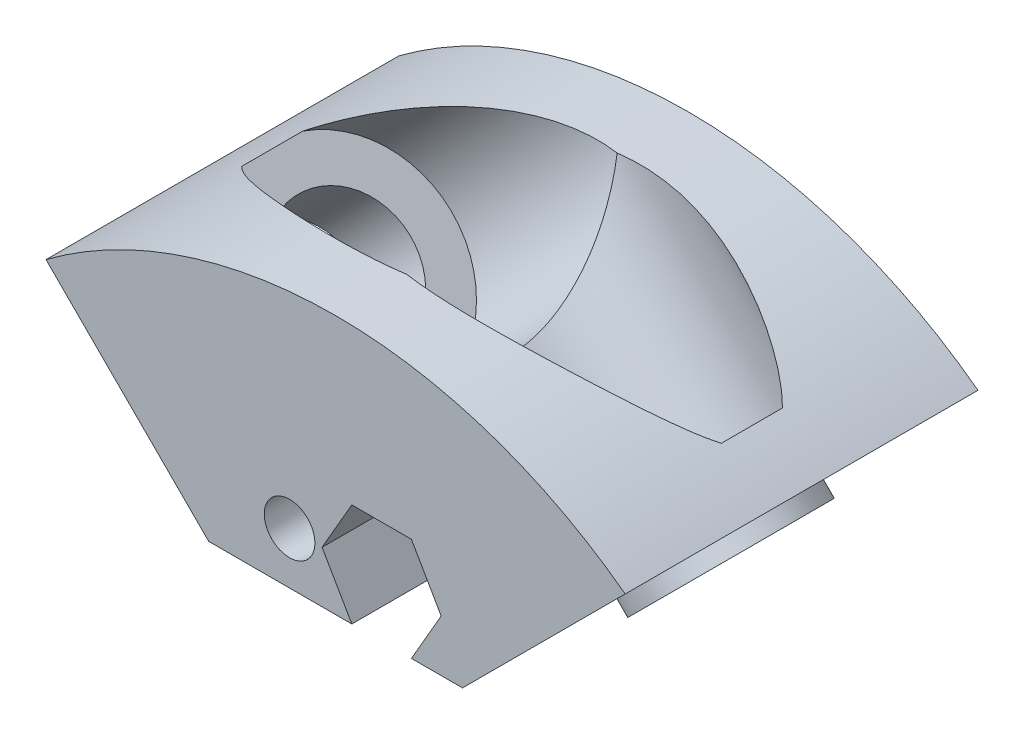
SolidWorks part; units mm, degrees
ref_plane "Front Plane" through (0, 0, 0) normal (0, 0, 1) x (1, 0, 0)
ref_plane "Top Plane" through (0, 0, 0) normal (0, 1, 0) x (1, 0, 0)
ref_plane "Right Plane" through (0, 0, 0) normal (1, 0, 0) x (0, 0, -1)
sketch "Sketch4" plane through (0, 0, 0) normal (0, 0, 1) x (1, 0, 0)
  line L0 (-6.5054, 11.4551) -> (-22.0617, 27.0115) construction
  line L1 (-6.5054, 11.4551) -> (-11.4551, 6.5054) construction
  line L2 (-22.0617, 27.0115) -> (-27.0115, 22.0617) construction
  line L3 (-11.4551, 6.5054) -> (-27.0115, 22.0617) construction
  line L4 (-6.5054, 11.4551) -> (-27.0115, 22.0617) construction
  line L5 (-22.0617, 27.0115) -> (-11.4551, 6.5054) construction
  line L6 (27.0115, 22.0617) -> (11.4551, 6.5054) construction
  line L7 (27.0115, 22.0617) -> (22.0617, 27.0115) construction
  line L8 (11.4551, 6.5054) -> (6.5054, 11.4551) construction
  line L9 (22.0617, 27.0115) -> (6.5054, 11.4551) construction
  line L10 (27.0115, 22.0617) -> (6.5054, 11.4551) construction
  line L11 (11.4551, 6.5054) -> (22.0617, 27.0115) construction
  line L12 (0, 0) -> (24.5366, 24.5366) construction
  line L13 (0, 0) -> (-8.9803, 8.9803) construction
  line L14 (0, -981.4314) -> (0, 49018.5686) construction
  line L15 (-18.8798, 25.2437) -> (-8.2731, 14.6371)
  line L16 (8.2731, 14.6371) -> (18.8798, 25.2437)
  line L17 (-16.7584, 16.7584) -> (-13.5765, 19.9404) construction
  line L18 (16.7584, 16.7584) -> (13.5765, 19.9404) construction
  line L19 (-18.1726, 23.1224) -> (-10.3945, 15.3442)
  line L20 (18.1726, 23.1224) -> (10.3945, 15.3442)
  line L21 (-10.3945, 15.3442) -> (-9.6874, 16.0513)
  line L22 (-9.6874, 16.0513) -> (-8.2731, 14.6371)
  line L23 (10.3945, 15.3442) -> (9.6874, 16.0513)
  line L24 (9.6874, 16.0513) -> (8.2731, 14.6371)
  line L25 (18.1726, 23.1224) -> (17.4655, 23.8295)
  line L26 (17.4655, 23.8295) -> (18.8798, 25.2437)
  line L27 (-18.8798, 25.2437) -> (-17.4655, 23.8295)
  line L28 (-17.4655, 23.8295) -> (-18.1726, 23.1224)
  line L29 (-14.2836, 19.2333) -> (-13.5765, 19.9404)
  line L30 (14.2836, 19.2333) -> (13.5765, 19.9404)
  line L31 (17.3241, 22.2739) -> (16.617, 22.981)
  line L32 (-17.3241, 22.2739) -> (-16.617, 22.981)
  line L33 (-8.2731, 14.6371) -> (8.2731, 14.6371)
  circle A0 centre (0, 0) radius 12.7 construction
  circle A1 centre (0, 0) radius 23.7 construction
  arc A3 (-18.8798, 25.2437) -> (18.8798, 25.2437) centre (0, 0) cw
  point P4 (-16.7584, 16.7584)
  point P5 (16.7584, 16.7584)
  point P26 (13.5765, 19.9404)
  point P32 (-14.2836, 19.2333)
  point P33 (14.2836, 19.2333)
  dimension "D1" = 25.4
  dimension "D2" = 11
  dimension "D3" = 22
  dimension "D4" = 7
  dimension "D5" = 45
  dimension "D6" = 45
  dimension "D7" = 1
  dimension "D8" = 15
  dimension "D9" = 4.3
  dimension "D10" = 4.3
extrude "Boss-Extrude1" add sketch "Sketch4" along normal mid plane 23 contours A3 L15 L33 L16 region at (0, 23.1989, 0)
revolve "Revolve1" add sketch "Sketch4<3>" angle 360 about L29 region at (-17.3948, 23.0517, 0)
sketch "Sketch4<3>" plane through (0, 0, 0) normal (0, 0, 1) x (1, 0, 0) same geometry as "Sketch4"
sketch "Sketch7" plane through (3.182, 3.182, 0) normal (-0.7071, -0.7071, 0) x (0, 0, 1)
  circle A0 centre (0, 23.7) radius 4.3
  circle A1 centre (0, 23.7) radius 4.3 construction
  circle A2 centre (0, 23.7) radius 7
  circle M1 centre (0, 23.7) radius 4.3
  dimension "D1" = 14
extrude "Cut-Extrude5" cut sketch "Sketch7" against normal through all both and the other way through all contours M1 region at (-13.5765, 19.9404, 0)
extrude "Cut-Extrude6" cut sketch "Sketch7<3>" against normal through all from offset 3.8 offset against normal yes
sketch "Sketch7<3>" plane through (3.182, 3.182, 0) normal (-0.7071, -0.7071, 0) x (0, 0, 1) same geometry as "Sketch7"
mirror "Mirror2" about plane through (0, 0, 0) normal (1, 0, 0) of "Cut-Extrude6", "Revolve1", "Cut-Extrude5"
sketch "Sketch8" plane through (0, 0, 0) normal (0, 0, 1) x (1, 0, 0)
  line L0 (-3, 18) -> (3, 18) construction
  line L1 (-8.2731, 14.6371) -> (8.2731, 14.6371) construction
  line L2 (-6.8831, 18) -> (-4.9416, 14.6371)
  line L3 (-4.9416, 14.6371) -> (-1.0584, 14.6371)
  line L4 (-1.0584, 14.6371) -> (0.8831, 18)
  line L5 (0.8831, 18) -> (-1.0584, 21.3629)
  line L6 (-1.0584, 21.3629) -> (-4.9416, 21.3629)
  line L7 (-4.9416, 21.3629) -> (-6.8831, 18)
  line L8 (6.8831, 18) -> (4.9416, 21.3629)
  line L9 (4.9416, 21.3629) -> (1.0584, 21.3629)
  line L10 (1.0584, 21.3629) -> (-0.8831, 18)
  line L11 (-0.8831, 18) -> (1.0584, 14.6371)
  line L12 (1.0584, 14.6371) -> (4.9416, 14.6371)
  line L13 (4.9416, 14.6371) -> (6.8831, 18)
  circle A0 centre (-3, 18) radius 1.65
  circle A1 centre (3, 18) radius 1.65
  circle A4 centre (-3, 18) radius 3.3629 construction
  circle A5 centre (3, 18) radius 3.3629 construction
  point P4 (0, 18)
  dimension "D1" = 3.3
  dimension "D2" = 6
  dimension "D3" = 18
extrude "Cut-Extrude7" cut sketch "Sketch8" against normal through all both and the other way through all contours A0 | A1 region at (-3, 18, 0) region at (3, 18, 0)
extrude "Cut-Extrude8" cut sketch "Sketch8<3>" against normal through all from offset 5 contours A0 | L10 L11 L4 L5 region at (-5.829, 19.6333, 0) region at (0, 18, 0) offset against normal yes
sketch "Sketch8<3>" plane through (0, 0, 0) normal (0, 0, 1) x (1, 0, 0) same geometry as "Sketch8"
extrude "Cut-Extrude9" cut sketch "Sketch8<4>" along normal through all from offset 5 contours A1 | L10 L11 L4 L5 region at (0, 18, 0) region at (0.5249, 17.1871, 0)
sketch "Sketch8<4>" plane through (0, 0, 0) normal (0, 0, 1) x (1, 0, 0) same geometry as "Sketch8"
